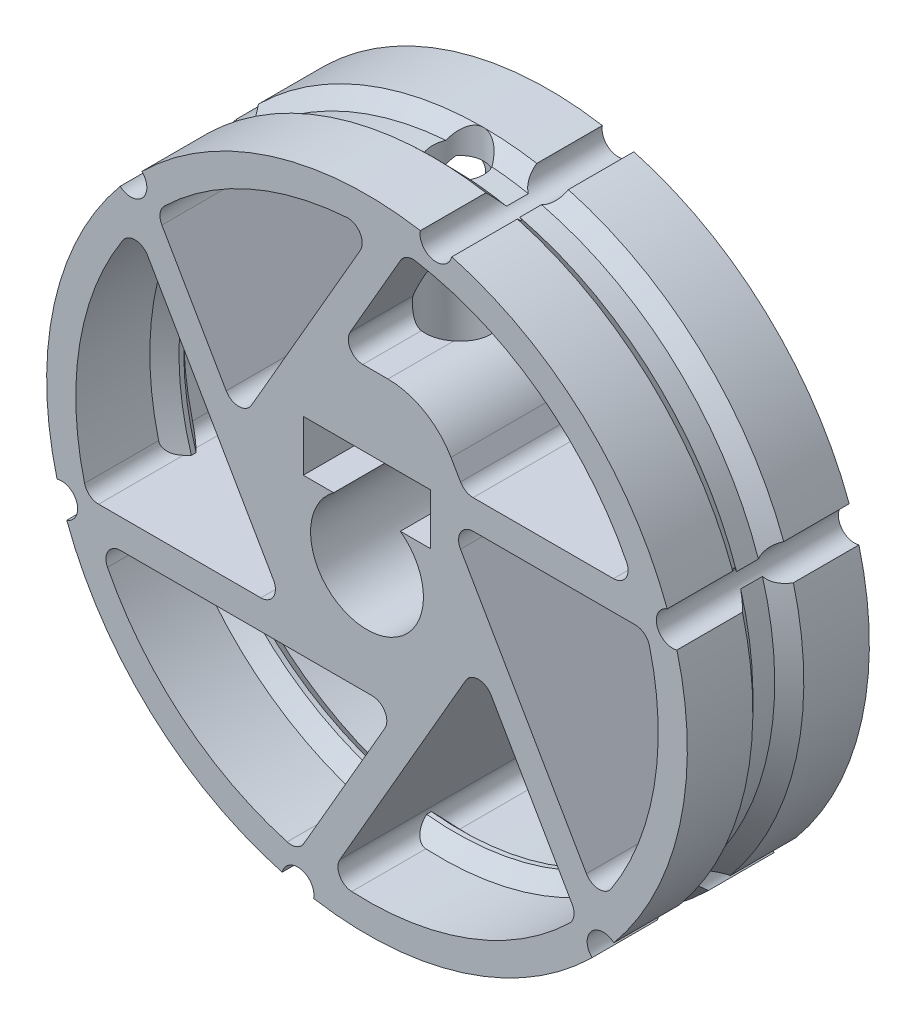
SolidWorks part; units mm, degrees
ref_plane "Front Plane" through (0, 0, 0) normal (0, 0, 1) x (1, 0, 0)
ref_plane "Top Plane" through (0, 0, 0) normal (0, 1, 0) x (1, 0, 0)
ref_plane "Right Plane" through (0, 0, 0) normal (1, 0, 0) x (0, 0, -1)
sketch "Sketch1" plane through (0, 0, 0) normal (0, 0, 1) x (1, 0, 0)
  line L0 (1.833, 2.5) -> (3.5, 2.5)
  line L1 (3.5, 2.5) -> (3.5, 5.3)
  line L2 (3.5, 5.3) -> (-3.5, 5.3)
  line L3 (-3.5, 5.3) -> (-3.5, 2.5)
  line L4 (-3.5, 2.5) -> (-1.833, 2.5)
  line L5 (-1.6583, 2.5) -> (1.6583, 2.5) construction
  line L6 (-7.0437, 0) -> (-12.6785, 9.7599)
  line L7 (3.5218, -6.1) -> (7.0437, 0) construction
  line L8 (7.0437, 0) -> (3.5218, 6.1) construction
  line L9 (3.5218, 6.1) -> (-3.5218, 6.1) construction
  line L10 (-3.5218, 6.1) -> (-7.0437, 0) construction
  line L11 (-7.0437, 0) -> (-3.5218, -6.1) construction
  line L12 (-3.5218, -6.1) -> (3.5218, -6.1) construction
  line L13 (-3.5218, -6.1) -> (-14.7916, -6.1)
  line L14 (3.5218, -6.1) -> (-2.113, -15.8599)
  line L15 (7.0437, 0) -> (12.6785, -9.7599)
  line L16 (-6.1199, 1.6) -> (-11.5742, 11.0471) construction
  line L17 (6.1199, -1.6) -> (11.5742, -11.0471)
  line L18 (1.6743, -6.1) -> (-3.78, -15.5471)
  line L19 (-4.4456, -4.5) -> (-15.3542, -4.5)
  line L20 (3.5218, 6.1) -> (14.7916, 6.1) construction
  line L21 (4.4456, 4.5) -> (15.3542, 4.5)
  line L22 (-11.5742, 11.0471) -> (-7.0437, 3.2)
  line L23 (-7.0437, 3.2) -> (-3.4613, 9.4048)
  line L24 (-3.4613, 9.4048) -> (3.4613, 9.4048) construction
  line L25 (3.4613, 9.4048) -> (5.3694, 6.1)
  line L26 (5.3694, 6.1) -> (14.7916, 6.1)
  line L29 (-7.0437, 0) -> (-4.4456, -4.5)
  line L30 (-3.5218, -6.1) -> (1.6743, -6.1)
  line L31 (3.5218, -6.1) -> (6.1199, -1.6)
  line L32 (7.0437, 0) -> (4.4456, 4.5)
  line L33 (-3.4613, 9.4048) -> (0.3443, 15.9963)
  line L34 (2.113, 15.8599) -> (-1.6138, 9.4048)
  line L35 (3.4613, 9.4048) -> (-1.6138, 9.4048)
  line L36 (10.0805, 6.1) -> (10.0805, 4.5) construction
  line L37 (-1.5585, 12.7005) -> (-0.1729, 11.9005) construction
  circle A0 centre (0, 0) radius 3 construction
  circle A1 centre (0, 0) radius 3.1 construction
  arc A2 (-1.833, 2.5) -> (1.833, 2.5) centre (0, 0) ccw
  circle A3 centre (0, 0) radius 6.1 construction
  circle A4 centre (0, 0) radius 20 construction
  circle A6 centre (0, 0) radius 17.6
  circle A7 centre (0, 0) radius 16 construction
  arc A8 (0.3443, 15.9963) -> (-11.5742, 11.0471) centre (0, 0) ccw
  arc A9 (-12.6785, 9.7599) -> (-15.3542, -4.5) centre (0, 0) ccw
  arc A10 (-3.78, -15.5471) -> (-14.7916, -6.1) centre (0, 0) cw
  arc A11 (11.5742, -11.0471) -> (-2.113, -15.8599) centre (0, 0) cw
  arc A12 (15.3542, 4.5) -> (12.6785, -9.7599) centre (0, 0) cw
  arc A13 (14.7916, 6.1) -> (2.113, 15.8599) centre (0, 0) ccw
  point P13 (0, -3)
  point P43 (0, 9.4048)
  point P55 (-17.6, 0)
  point P56 (17.6, 0)
  point P58 (0, -17.6)
  point P59 (0, 17.6)
  point P61 (-16, 0)
  dimension "D1" = 6
  dimension "D7" = 40
  dimension "D3" = 7
  dimension "D4" = 2.8
  dimension "D5" = 5.5
  dimension "D6" = 0.8
  dimension "D10" = 1.6
  dimension "D11" = 4.1048
  dimension "D12" = 1.6
  dimension "D2" = 0.1
  dimension "D8" = 2.4
  dimension "D9" = 1.6
extrude "Boss-Extrude1" add sketch "Sketch1" along normal blind 10
ref_axis "Axis1" through (0, 0, 10) along (0, 0, -1)
fillet "Fillet1" radius 0.8 7 edges at (4.4456, 4.5, 5) (6.1199, -1.6, 5) (1.6743, -6.1, 5) (-4.4456, -4.5, 5) (-7.0437, 3.2, 5) (-1.6138, 9.4048, 5) (5.3694, 6.1, 5)
fillet "Fillet2" radius 0.8 6 edges at (12.6785, -9.7599, 5) (14.7916, 6.1, 5) (-12.6785, 9.7599, 5) (-14.7916, -6.1, 5) (-2.113, -15.8599, 5) (0.3443, 15.9963, 5)
fillet "Fillet3" radius 0.8 6 edges at (-15.3542, -4.5, 5) (-11.5742, 11.0471, 5) (15.3542, 4.5, 5) (11.5742, -11.0471, 5) (-3.78, -15.5471, 5) (2.113, 15.8599, 5)
fillet "Fillet4" radius 4 1 edges at (3.4613, 9.4048, 5)
sketch "Sketch2" plane through (0, 5.3, 0) normal (0, -1, 0) x (1, 0, 0)
  line L0 (0, 10) -> (0, 0) construction
  line L1 (3.5, 10) -> (-3.5, 10) construction
  line L2 (3.5, 0) -> (-3.5, 0) construction
  circle A0 centre (0, 5) radius 1.8
  point P8 (0, 0)
  point P9 (0, 0)
  dimension "D1" = 3.6
extrude "Cut-Extrude1" cut sketch "Sketch2" against normal up to surface (10.5984 mm away) up to face at (8.9666, 12.2074, 5)
sketch "Sketch5" plane through (0, 0, 0) normal (0, 1, 0) x (1, 0, 0)
  line L0 (-17.6, -3.6) -> (-17.6, -6.4)
  line L3 (-17.6, -3.6) -> (-16.8, -4.4)
  line L4 (-16.8, -4.4) -> (-16.8, -5.6)
  line L5 (-16.8, -5.6) -> (-17.6, -6.4)
  point P2 (-16.8599, -5.2795)
  point P3 (-17.6, -5)
  point P9 (-16.8, -5.5365)
  point P11 (-17.0478, -4.4)
  dimension "D1" = 0.8
  dimension "D2" = 45
  dimension "D3" = 1.2
sketch "Sketch7" plane through (0, 0, 0) normal (0, 1, 0) x (1, 0, 0)
  line L0 (-17.6, -2.4686) -> (-17.6, -7.5314)
  line L1 (-17.6, -7.5314) -> (-15.2, -5.1314)
  line L2 (-15.2, -5.1314) -> (-15.2, -4.8686)
  line L3 (-15.2, -4.8686) -> (-17.6, -2.4686)
  line L4 (-16.8, -5.6) -> (-17.6, -6.4) construction
  line L5 (-17.6, -3.6) -> (-17.6, -6.4) construction
  line L6 (-16.8, -4.4) -> (-16.8, -5.6) construction
  point P6 (-17.6, -5)
  dimension "D1" = 1.6
  dimension "D2" = 0.8
revolve "Revolve1" add sketch "Sketch7" angle 360 about axis through (0, 0, 10) along (0, 0, -1)
sketch "Sketch6" plane through (0, 5.3, 0) normal (0, -1, 0) x (1, 0, 0)
  circle A0 centre (0, 5) radius 1.4
  dimension "D1" = 2.8
extrude "Cut-Extrude3" cut sketch "Sketch6" against normal through all
sketch "Sketch3" plane through (0, 0, 10) normal (0, 0, 1) x (1, 0, 0)
  line L0 (2.5981, -6.1) -> (-3.8016, -17.1845) construction
  line L1 (-3.5218, -6.1) -> (3.5218, -6.1) construction
  line L2 (1.6743, -6.1) -> (-3.78, -15.5471) construction
  line L3 (1.6743, -6.1) -> (3.5218, -6.1) construction
  circle A0 centre (-3.8016, -17.1845) radius 0.8863
  circle A1 centre (0, 0) radius 17.6 construction
  circle A2 centre (0, 0) radius 16 construction
  circle A3 centre (-16.783, -5.3) radius 0.8863
  circle A4 centre (-12.9814, 11.8845) radius 0.8863
  circle A5 centre (3.8016, 17.1845) radius 0.8863
  circle A6 centre (16.783, 5.3) radius 0.8863
  circle A7 centre (12.9814, -11.8845) radius 0.8863
  point P14 (2.5981, -6.1)
  point P15 (-3.3584, -16.4169)
  point P16 (-2.9584, -15.7241)
  point P17 (0, 0)
  point P32 (0, 0)
  dimension "D1" = 0.8
  dimension "D2" = 6
extrude "Cut-Extrude2" cut sketch "Sketch3" against normal through all
revolve "Cut-Revolve2" cut sketch "Sketch5" angle 360 about axis through (0, 0, 10) along (0, 0, -1)
